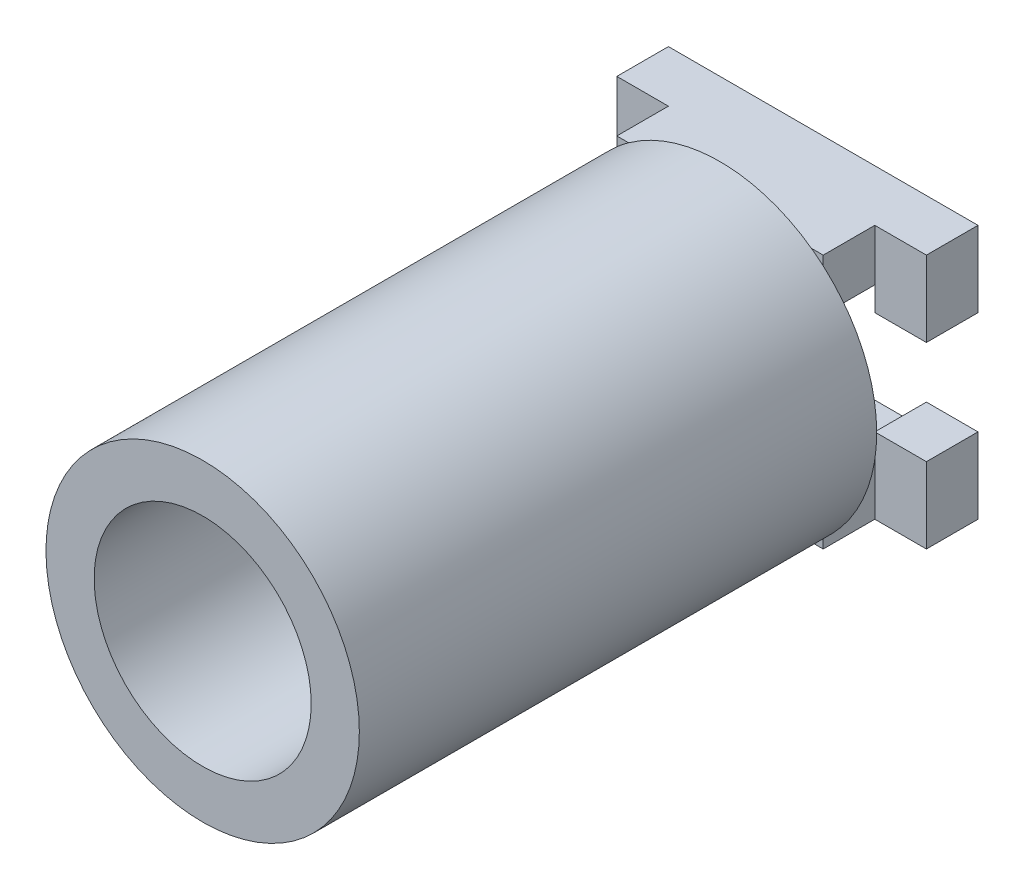
SolidWorks part; units mm, degrees
ref_plane "Front Plane" through (0, 0, 0) normal (0, 0, 1) x (1, 0, 0)
ref_plane "Top Plane" through (0, 0, 0) normal (0, 1, 0) x (1, 0, 0)
ref_plane "Right Plane" through (0, 0, 0) normal (1, 0, 0) x (0, 0, -1)
sketch "Sketch1" plane through (0, 0, 0) normal (0, 0, 1) x (1, 0, 0)
  circle A2 centre (-7.6717, 4.7989) radius 4.555
  circle A4 centre (-7.6717, 4.7989) radius 3.155
  circle A5 centre (-7.6717, 4.7989) radius 3.155
  dimension "D1" = 0.1
extrude "Boss-Extrude1" add sketch "Sketch1" along normal up to surface (7.64 mm away)
sketch "Sketch2" plane through (0, 0, 0) normal (0, 0, -1) x (-1, 0, 0)
  line L4 (10.8417, 5.2839) -> (4.5017, 5.2839)
  line L5 (4.5017, 5.2839) -> (4.5017, 3.5839)
  line L6 (4.5017, 3.5839) -> (10.8417, 3.5839)
  line L7 (10.8417, 3.5839) -> (10.8417, 5.2839)
  line L8 (10.8417, 5.2839) -> (4.5017, 5.2839)
  line L9 (4.5017, 5.2839) -> (4.5017, 3.5839)
  line L10 (4.5017, 3.5839) -> (10.8417, 3.5839)
  line L11 (10.8417, 3.5839) -> (10.8417, 5.2839)
  circle A0 centre (7.6717, 4.7989) radius 3.155 construction
  circle A1 centre (7.6717, 4.7989) radius 3.155
  circle M5 centre (7.6717, 4.7989) radius 4.555
  circle M6 centre (7.6717, 4.7989) radius 3.155
  dimension "D1" = 0
extrude "Boss-Extrude2" add sketch "Sketch2" along normal up to surface (5.9 mm away) contours L11 L10 L9 L8 M5 M6 region at (-3.2455, 4.7989, 0)
sketch "Sketch3" plane through (0, 0, -5.9) normal (0, 0, -1) x (-1, 0, 0)
  line L0 (7.6717, 7.7989) -> (7.6717, 1.7989) construction
  line L1 (7.6717, 9.3539) -> (7.6717, 0.2439)
  circle A0 centre (7.6717, 4.7989) radius 4.555 construction
  circle A1 centre (7.6717, 4.7989) radius 4.555
  line M1 (10.8417, 5.2839) -> (10.8417, 3.5839)
  line M2 (10.8417, 3.5839) -> (10.5834, 3.5839)
  arc M3 (10.5834, 3.5839) -> (4.76, 3.5839) centre (7.6717, 4.7989) cw
  line M4 (4.76, 3.5839) -> (4.5017, 3.5839)
  line M5 (4.5017, 3.5839) -> (4.5017, 5.2839)
  line M6 (4.5017, 5.2839) -> (4.5542, 5.2839)
  arc M7 (4.5542, 5.2839) -> (10.7892, 5.2839) centre (7.6717, 4.7989) cw
  line M8 (10.7892, 5.2839) -> (10.8417, 5.2839)
  circle M9 centre (7.6717, 4.7989) radius 4.555
extrude "Boss-Extrude3" add sketch "Sketch3" along normal blind 1.5 contours L1 M9 M7 M8 M1 M2 M3 | L1 M7 M3 M2 M1 M8 | L1 M9 M3 M4 M5 M6 M7 region at (-10.8206, 7.9477, -5.9) region at (-7.5699, 8.6539, -5.9) region at (-9.0251, 4.7928, -5.9)
sketch "Sketch4" plane through (0, 0, -7.4) normal (0, 0, -1) x (-1, 0, 0)
  line L0 (10.6717, 4.7989) -> (4.6717, 4.7989) construction
  line L1 (7.6717, 8.4989) -> (10.6717, 8.4989)
  line L2 (7.6717, 8.4989) -> (7.6717, 1.0989)
  line L3 (7.6717, 1.0989) -> (10.6717, 1.0989)
  line L4 (10.6717, 8.4989) -> (10.6717, 1.0989)
  line L5 (7.6717, 8.4989) -> (10.6717, 1.0989) construction
  line L6 (7.6717, 1.0989) -> (10.6717, 8.4989) construction
  line L7 (7.6717, 7.9539) -> (7.6717, 1.6439) construction
  line L8 (6.1717, 6.9989) -> (6.1717, 8.4989) construction
  line L9 (4.6717, 8.4989) -> (7.6717, 8.4989)
  line L10 (4.6717, 8.4989) -> (4.6717, 1.0989)
  line L11 (4.6717, 1.0989) -> (7.6717, 1.0989)
  line L12 (7.6717, 8.4989) -> (7.6717, 1.0989)
  line L13 (4.6717, 8.4989) -> (7.6717, 1.0989) construction
  line L14 (4.6717, 1.0989) -> (7.6717, 8.4989) construction
  line L15 (10.6717, 8.4989) -> (12.1717, 8.4989)
  line L16 (10.6717, 8.4989) -> (10.6717, 6.2989)
  line L17 (10.6717, 6.2989) -> (12.1717, 6.2989)
  line L18 (12.1717, 8.4989) -> (12.1717, 6.2989)
  line L19 (10.6717, 1.0989) -> (12.1717, 1.0989)
  line L20 (10.6717, 1.0989) -> (10.6717, 3.2989)
  line L21 (10.6717, 3.2989) -> (12.1717, 3.2989)
  line L22 (12.1717, 1.0989) -> (12.1717, 3.2989)
  line L23 (4.6717, 1.0989) -> (3.1717, 1.0989)
  line L24 (4.6717, 1.0989) -> (4.6717, 3.2989)
  line L25 (4.6717, 3.2989) -> (3.1717, 3.2989)
  line L26 (3.1717, 1.0989) -> (3.1717, 3.2989)
  line L27 (4.6717, 8.4989) -> (3.1717, 8.4989)
  line L28 (4.6717, 8.4989) -> (4.6717, 6.2989)
  line L29 (4.6717, 6.2989) -> (3.1717, 6.2989)
  line L30 (3.1717, 8.4989) -> (3.1717, 6.2989)
  line L31 (4.6717, 1.0989) -> (7.6717, 1.0989)
  line L32 (4.6717, 1.0989) -> (4.6717, 2.5989)
  line L33 (4.6717, 2.5989) -> (7.6717, 2.5989)
  line L34 (7.6717, 1.0989) -> (7.6717, 2.5989)
  line L35 (4.6717, 8.4989) -> (7.6717, 8.4989)
  line L36 (4.6717, 8.4989) -> (4.6717, 6.9989)
  line L37 (4.6717, 6.9989) -> (7.6717, 6.9989)
  line L38 (7.6717, 8.4989) -> (7.6717, 6.9989)
  line L39 (6.1717, 2.5989) -> (6.1717, 1.0989) construction
  point P0 (9.1717, 4.7989)
  point P9 (6.1717, 4.7989)
  circle M18 centre (7.6717, 4.7989) radius 4.555
  line M19 (7.6717, 7.9539) -> (7.6717, 1.6439)
  arc M44 (4.5542, 5.2839) -> (7.6717, 7.9539) centre (7.6717, 4.7989) cw
  arc M45 (7.6717, 1.6439) -> (4.76, 3.5839) centre (7.6717, 4.7989) cw
  dimension "D1" = 3
  dimension "D2" = 7.4
  dimension "D3" = 3
  dimension "D4" = 1.5
extrude "Boss-Extrude4" add sketch "Sketch4" along normal blind 3 contours L4 L1 L12 L3 M18 M19 | L10 L37 L9 M19 | L33 L24 L11 L12 | L4 L1 M18 | L4 L3 M18 | L9 L10 M18 | L10 L11 M18 | L33 L12 M45 | L37 M44 M19 region at (-9.166, 4.7989, -7.4) region at (-5.8754, 7.921, -7.4) region at (-10.5592, 8.4096, -7.4) region at (-6.8035, 7.3863, -7.4) region at (-4.7842, 8.4096, -7.4) region at (-6.8035, 2.2115, -7.4) region at (-5.8754, 1.6768, -7.4) region at (-10.5592, 1.1882, -7.4) region at (-4.7842, 1.1882, -7.4)
extrude "Boss-Extrude5" add sketch "Sketch4<3>" along normal blind 1.5 from offset 1.5 contours L18 L15 L4 L17 M18 | L4 L17 M18 | L19 L22 L21 L4 M18 | L21 L4 M18 | L27 L30 L29 L28 L10 | L26 L23 L24 L10 L25 | L29 L28 L10 M18 | L10 L25 L24 M18 region at (-11.6471, 7.7288, -7.4) region at (-11.1474, 6.9974, -7.4) region at (-4.196, 6.9974, -7.4) region at (-3.6963, 7.7288, -7.4) region at (-4.196, 2.6004, -7.4) region at (-11.1474, 2.6004, -7.4) region at (-3.6963, 1.869, -7.4) region at (-11.6471, 1.869, -7.4)
sketch "Sketch4<3>" plane through (0, 0, -7.4) normal (0, 0, -1) x (-1, 0, 0) same geometry as "Sketch4"
